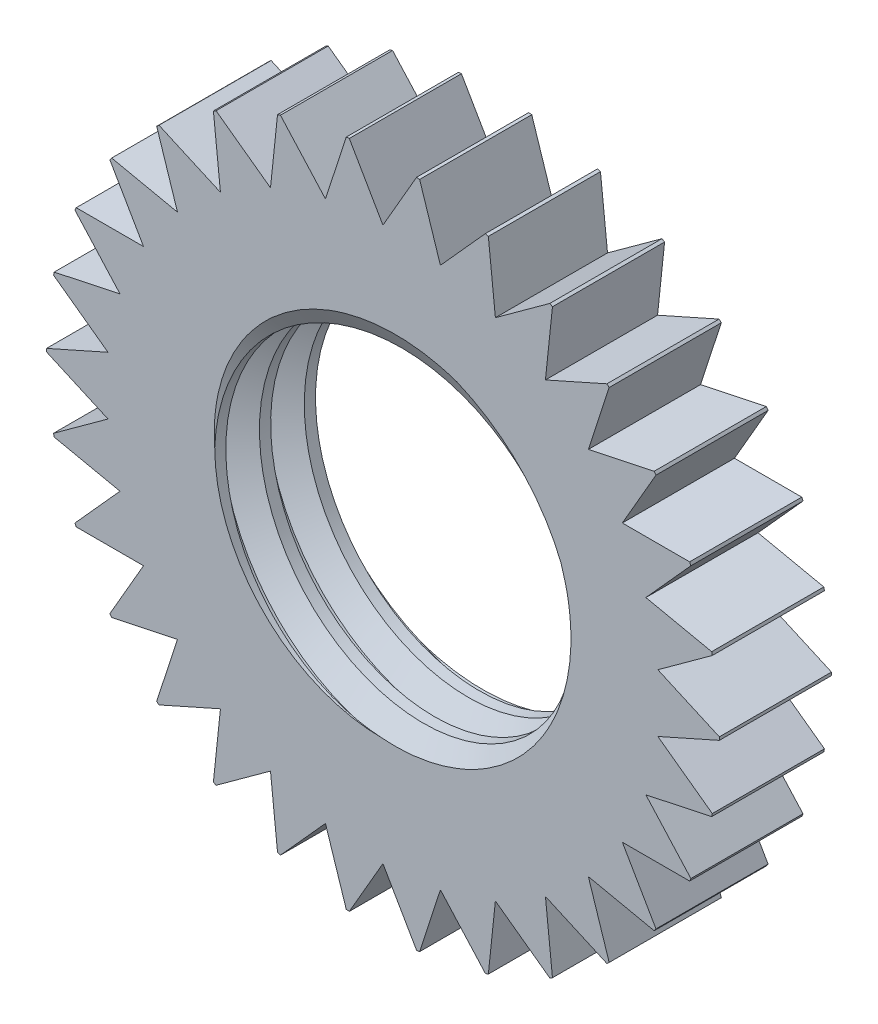
SolidWorks part; units mm, degrees
ref_plane "Front Plane" through (0, 0, 0) normal (0, 0, 1) x (1, 0, 0)
ref_plane "Top Plane" through (0, 0, 0) normal (0, 1, 0) x (1, 0, 0)
ref_plane "Right Plane" through (0, 0, 0) normal (1, 0, 0) x (0, 0, -1)
sketch "Sketch1" plane through (0, 0, 0) normal (0, 0, 1) x (1, 0, 0)
  circle A0 centre (0, 0) radius 7.5
  circle A1 centre (0, 0) radius 15
  dimension "D1" = 15
  dimension "D2" = 30
extrude "Boss-Extrude1" add sketch "Sketch1" along normal blind 5
thread "Thread1" pitch 2 method cut profile "Thread Profile1" start angle 0, offset 2, length 0, pitch 2, diameter 15
ref_plane "Plane1" through (7.5, 0, -2) normal (0, -1, 0) x (1, 0, 0)
sketch "Thread Profile1" plane through (7.5, 0, -2) normal (0, -1, 0) x (1, 0, 0)
  line L0 (0, 0) -> (0, 2) construction
  line L1 (0, 0) -> (1.0825, 0.625)
  line L2 (1.0825, 0.625) -> (1.0825, 0.875)
  line L3 (1.0825, 0.875) -> (0, 1.5)
  line L4 (1.0825, 0.75) -> (0, 0.75) construction
  line L11 (0, 0) -> (0, 1.5)
  point P2 (0, 0)
  dimension "Pitch" = 2
  dimension "Profile_Angle" = 60
  dimension "Profile_Land" = 0.25
  dimension "Profile_Height" = 1.0825
sketch "Sketch5" plane through (0, 0, 5) normal (0, 0, 1) x (1, 0, 0)
  line L0 (-13.6753, 6.1634) -> (-10.6753, 6.1634)
  line L1 (-10.6753, 6.1634) -> (-12.1753, 8.7614)
  circle A0 centre (0, 0) radius 15 construction
  dimension "D1" = 3
  dimension "D2" = 3
  dimension "D3" = 3
extrude "Cut-Extrude1" cut sketch "Sketch5" against normal blind 5 and the other way through all
pattern_circular "CirPattern1" count 30 every 12 about axis through (0, 0, 5) along (0, 0, 1) of "Cut-Extrude1"
